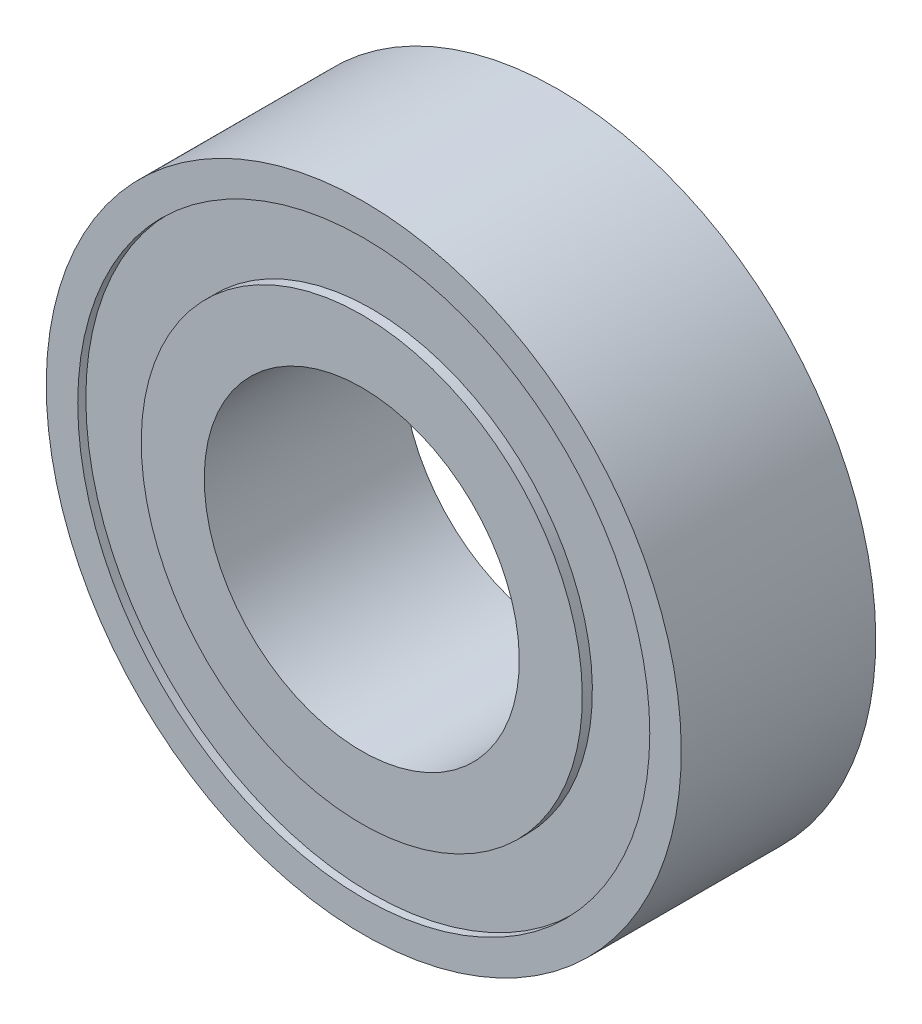
SolidWorks part; units mm, degrees
ref_plane "Front (1)" through (0, 0, 0) normal (0, 0, 1) x (1, 0, 0)
ref_plane "Top (2)" through (0, 0, 0) normal (0, 1, 0) x (1, 0, 0)
ref_plane "Right (3)" through (0, 0, 0) normal (1, 0, 0) x (0, 0, -1)
ref_axis "X-Axis" through (-80.9, 0, 0) along (1, 0, 0)
ref_axis "Y-Axis" through (0, -50, 0) along (0, 1, 0)
ref_axis "Z-Axis" through (0, 0, 50) along (0, 0, -1)
sketch "Sketch1" plane through (0, 0, 0) normal (1, 0, 0) x (0, 0, -1)
  line L0 (0, 0) -> (-5, 0) construction
  line L1 (-5, 3.9687) -> (0, 3.9688)
  line L2 (-5, 3.9687) -> (-5, 5.5562)
  line L3 (-5, 5.5562) -> (-4.746, 5.5562)
  line L4 (-4.746, 5.5562) -> (-4.746, 7.2062)
  line L5 (-4.746, 7.2062) -> (-4.95, 7.2062)
  line L6 (-4.95, 7.2062) -> (-4.95, 8)
  line L7 (-2.5, 8) -> (-2.5, 0) construction
  line L8 (-0.05, 8) -> (-4.95, 8)
  line L9 (-0.05, 7.2062) -> (-0.05, 8)
  line L10 (-0.254, 7.2062) -> (-0.05, 7.2062)
  line L11 (-0.254, 5.5562) -> (-0.254, 7.2062)
  line L12 (0, 5.5562) -> (-0.254, 5.5562)
  line L13 (0, 3.9688) -> (0, 5.5562)
  point P12 (-2.5, 0)
  point P19 (-2.5, 3.9687)
  dimension "D1" = 5
  dimension "D2" = 2.5
  dimension "D3" = 2.45
  dimension "D4" = 0.254
  dimension "D5" = 16
  dimension "D6" = 1.5875
  dimension "D7" = 0.7937
  dimension "D8" = 7.9375
revolve "Revolve1" add sketch "Sketch1" angle 360 about L0
